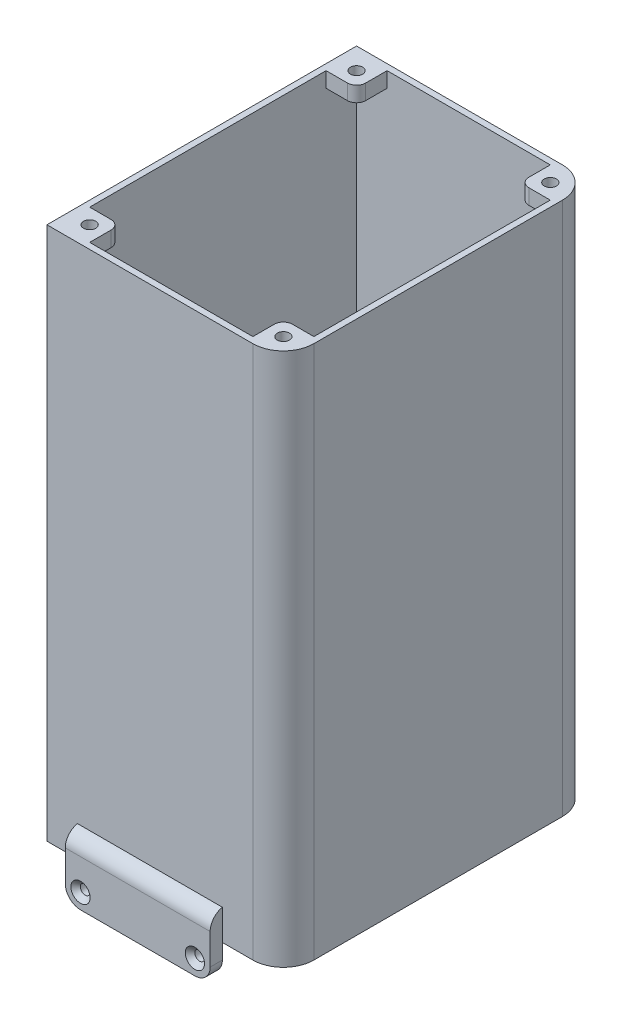
SolidWorks part; units mm, degrees
ref_plane "Front Plane" through (0, 0, 0) normal (0, 0, 1) x (1, 0, 0)
ref_plane "Top Plane" through (0, 0, 0) normal (0, 1, 0) x (1, 0, 0)
ref_plane "Right Plane" through (0, 0, 0) normal (1, 0, 0) x (0, 0, -1)
sketch "Sketch1" plane through (0, 0, 0) normal (0, 1, 0) x (1, 0, 0)
  line L1 (-38.75, -50.75) -> (28.75, -50.75)
  line L2 (-38.75, -50.75) -> (-38.75, 50.75)
  line L3 (-38.75, 50.75) -> (28.75, 50.75)
  line L4 (38.75, -40.75) -> (38.75, 40.75)
  line L5 (-38.75, -50.75) -> (38.75, 50.75) construction
  line L6 (-38.75, 50.75) -> (38.75, -50.75) construction
  line L7 (-36.75, 48.75) -> (26.75, 48.75)
  line L8 (-36.75, 48.75) -> (-36.75, -48.75)
  line L9 (-36.75, -48.75) -> (26.75, -48.75)
  line L10 (36.75, 38.75) -> (36.75, -38.75)
  arc A0 (28.75, -50.75) -> (38.75, -40.75) centre (28.75, -40.75) ccw
  arc A1 (28.75, 50.75) -> (38.75, 40.75) centre (28.75, 40.75) cw
  arc A2 (26.75, 48.75) -> (36.75, 38.75) centre (26.75, 38.75) cw
  arc A3 (26.75, -48.75) -> (36.75, -38.75) centre (26.75, -38.75) ccw
  point P0 (0, 0)
  dimension "D3" = 10
  dimension "D8" = 10
  dimension "D1" = 101.5
  dimension "D2" = 77.5
  dimension "D4" = 2
  dimension "D5" = 2
  dimension "D6" = 2
  dimension "D7" = 2
extrude "Boss-Extrude1" add sketch "Sketch1" along normal blind 170
sketch "Sketch2" plane through (0, 170, 0) normal (0, 1, 0) x (1, 0, 0)
  line L1 (-38.75, 50.75) -> (28.75, 50.75)
  line L2 (-38.75, 50.75) -> (-38.75, -50.75)
  line L3 (-38.75, -50.75) -> (28.75, -50.75)
  line L4 (38.75, 40.75) -> (38.75, -40.75)
  arc A0 (28.75, -50.75) -> (38.75, -40.75) centre (28.75, -40.75) ccw
  arc A1 (28.75, 50.75) -> (38.75, 40.75) centre (28.75, 40.75) cw
  dimension "D1" = 10
sketch "Sketch3" plane through (0, 170, 0) normal (0, 1, 0) x (1, 0, 0)
  line L0 (-38.75, 50.75) -> (28.75, 50.75)
  line L1 (-38.75, 50.75) -> (-38.75, -50.75)
  line L2 (-38.75, -50.75) -> (28.75, -50.75)
  line L3 (38.75, 40.75) -> (38.75, -40.75)
  line L4 (-36.75, 38.75) -> (-36.75, -38.75)
  line L5 (-36.75, 48.75) -> (-36.75, -48.75) construction
  line L8 (-36.75, -48.75) -> (26.75, -48.75) construction
  line L9 (-26.75, -48.75) -> (26.75, -48.75)
  line L12 (26.75, 48.75) -> (-36.75, 48.75) construction
  line L13 (-26.75, 48.75) -> (26.75, 48.75)
  line L16 (36.75, 38.75) -> (36.75, -38.75)
  line L19 (26.75, 48.75) -> (26.75, 41.75)
  line L20 (29.75, 38.75) -> (36.75, 38.75)
  line L21 (26.75, -48.75) -> (26.75, -41.75)
  line L22 (29.75, -38.75) -> (36.75, -38.75)
  line L23 (-36.75, -38.75) -> (-29.75, -38.75)
  line L24 (-26.75, -41.75) -> (-26.75, -48.75)
  line L25 (-36.75, 38.75) -> (-29.75, 38.75)
  line L26 (-26.75, 41.75) -> (-26.75, 48.75)
  arc A0 (28.75, 50.75) -> (38.75, 40.75) centre (28.75, 40.75) cw
  arc A1 (38.75, -40.75) -> (28.75, -50.75) centre (28.75, -40.75) cw
  arc A6 (-29.75, 38.75) -> (-26.75, 41.75) centre (-29.75, 41.75) ccw
  arc A7 (26.75, -41.75) -> (29.75, -38.75) centre (29.75, -41.75) cw
  circle A8 centre (-31.75, -43.75) radius 2
  circle A9 centre (-31.75, 43.75) radius 2
  circle A10 centre (31.75, 43.75) radius 2
  circle A11 centre (31.75, -43.75) radius 2
  arc A12 (-29.75, -38.75) -> (-26.75, -41.75) centre (-29.75, -41.75) cw
  arc A13 (26.75, 41.75) -> (29.75, 38.75) centre (29.75, 41.75) ccw
  point P38 (-26.75, 38.75)
  point P42 (26.75, -38.75)
  point P45 (-26.75, -38.75)
  point P48 (26.75, 38.75)
  dimension "D1" = 4
  dimension "D2" = 10
  dimension "D4" = 4
  dimension "D6" = 4
  dimension "D7" = 4
  dimension "D8" = 5
  dimension "D9" = 5
  dimension "D10" = 5
  dimension "D11" = 5
  dimension "D12" = 5
  dimension "D13" = 5
  dimension "D14" = 5
  dimension "D15" = 5
  dimension "D16" = 3
  dimension "D17" = 3
  dimension "D3" = 10
  dimension "D5" = 10
extrude "Boss-Extrude2" add sketch "Sketch3" along normal blind 5
ref_plane "Plane1" through (0, 10, 0) normal (0, -1, 0) x (-1, 0, 0)
sketch "Sketch4" plane through (0, 10, 0) normal (0, -1, 0) x (-1, 0, 0)
  line L0 (38.75, -50.75) -> (-28.75, -50.75) construction
  line L1 (-18.75, -50.75) -> (28.75, -50.75)
  line L2 (-18.75, -50.75) -> (-18.75, -54.75)
  line L3 (-18.75, -54.75) -> (28.75, -54.75)
  line L4 (28.75, -50.75) -> (28.75, -54.75)
  dimension "D1" = 10
  dimension "D2" = 10
  dimension "D3" = 4
extrude "Boss-Extrude3" add sketch "Sketch4" along normal blind 20
fillet "Fillet1" radius 5 2 edges at (18.75, -10, 52.75) (-28.75, -10, 52.75)
fillet "Fillet2" radius 5 1 edges at (-5, 10, 54.75)
hole_wizard "CSK for M3 Flat Head Machine Screw1" positions "Sketch5" profile "Sketch6" countersink size "M3" standard "ANSI Metric" end condition through all
sketch "Sketch5" plane through (0, 0, 54.75) normal (0, 0, 1) x (1, 0, 0)
  line L0 (13.75, -10) -> (-23.75, -10) construction
  line L1 (18.75, -5) -> (18.75, 5.101) construction
  line L2 (-28.75, -5) -> (-28.75, 5.101) construction
  point P0 (13.75, -5)
  point P2 (-23.75, -5)
  dimension "D1" = 5
  dimension "D2" = 5
  dimension "D3" = 5
  dimension "D4" = 5
sketch "Sketch6" plane through (13.75, -5, 54.75) normal (1, 0, 0) x (0, -1, 0)
  line L0 (0, 0) -> (0, 105.5)
  line L1 (0, 105.5) -> (1.6, 105.5)
  line L2 (1.6, 105.5) -> (1.6, 1.55)
  line L3 (1.6, 1.55) -> (3.15, 0)
  line L5 (3.15, 0) -> (0, 0)
  line L6 (-1.6, 1.55) -> (-3.15, 0) construction
  line L11 (0, -6.35) -> (0, 107.95) construction
  dimension "Thru Hole Dia." = 3.2
  dimension "Thru Hole Depth" = 105.5
  dimension "Near C'Sink Dia." = 6.3
  dimension "Near C'Sink Angle" = 90
mirror "Mirror1" about plane through (0, 0, 0) normal (0, 0, 1) of "CSK for M3 Flat Head Machine Screw1", "Fillet2", "Fillet1", "Boss-Extrude3"
